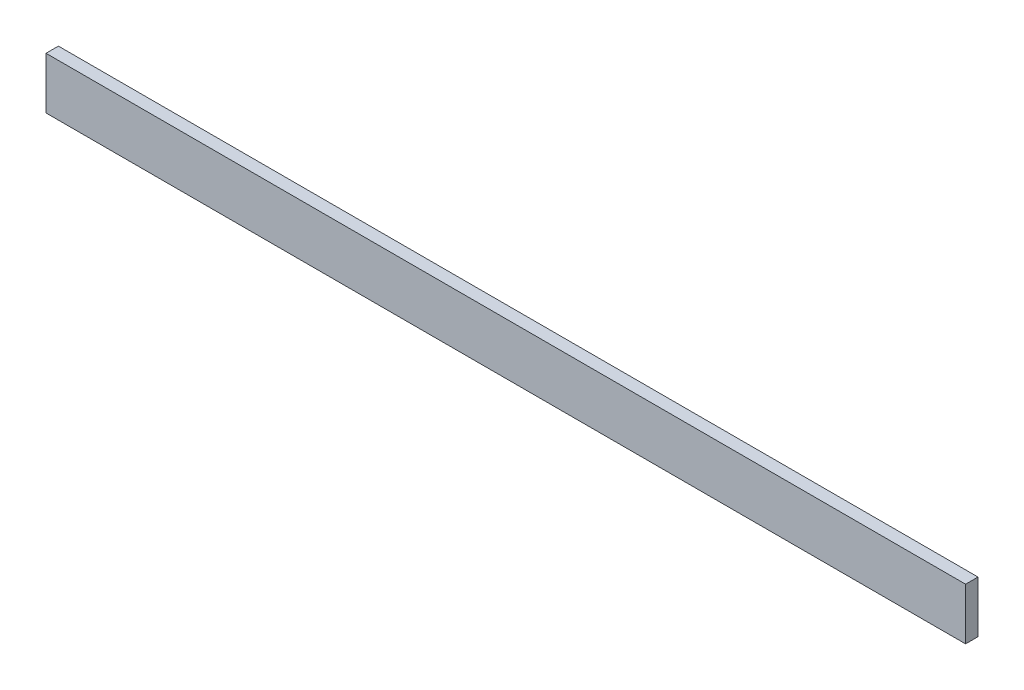
SolidWorks part; units mm, degrees
ref_plane "Front Plane" through (0, 0, 0) normal (0, 0, 1) x (1, 0, 0)
ref_plane "Top Plane" through (0, 0, 0) normal (0, 1, 0) x (1, 0, 0)
ref_plane "Right Plane" through (0, 0, 0) normal (1, 0, 0) x (0, 0, -1)
sketch "Sketch1" plane through (0, 0, 0) normal (0, 0, 1) x (1, 0, 0)
  line L1 (88.9, -5) -> (-88.9, -5)
  line L2 (88.9, -5) -> (88.9, 5)
  line L3 (88.9, 5) -> (-88.9, 5)
  line L4 (-88.9, -5) -> (-88.9, 5)
  line L5 (88.9, -5) -> (-88.9, 5) construction
  line L6 (88.9, 5) -> (-88.9, -5) construction
  point P0 (0, 0)
  dimension "D1" = 177.8
  dimension "D2" = 10
extrude "Boss-Extrude1" add sketch "Sketch1" along normal blind 2.4
